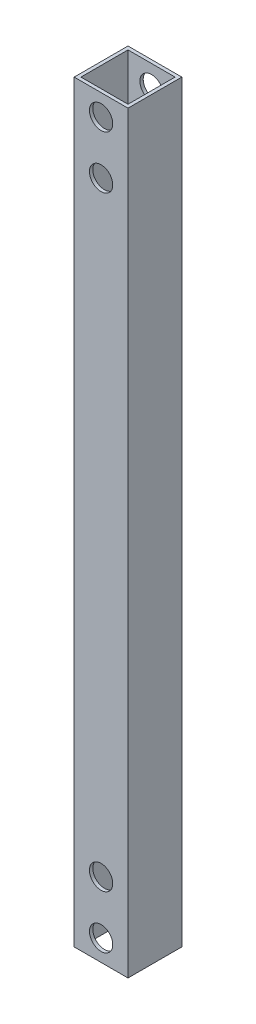
SolidWorks part; units mm, degrees
material "1060 Alloy"
ref_plane "Front Plane" through (0, 0, 0) normal (0, 0, 1) x (1, 0, 0)
ref_plane "Top Plane" through (0, 0, 0) normal (0, 1, 0) x (1, 0, 0)
ref_plane "Right Plane" through (0, 0, 0) normal (1, 0, 0) x (0, 0, -1)
sketch "Sketch1" plane through (0, 0, 0) normal (0, 1, 0) x (1, 0, 0)
  line L1 (-12.7, -12.7) -> (12.7, -12.7)
  line L2 (-12.7, -12.7) -> (-12.7, 12.7)
  line L3 (-12.7, 12.7) -> (12.7, 12.7)
  line L4 (12.7, -12.7) -> (12.7, 12.7)
  line L5 (-12.7, -12.7) -> (12.7, 12.7) construction
  line L6 (-12.7, 12.7) -> (12.7, -12.7) construction
  point P0 (0, 0)
  dimension "D1" = 25.4
extrude "Extrude-Thin1" add sketch "Sketch1" along normal blind 355.6 thin thin type one direction reverse wall 1.5875
sketch "Sketch2" plane through (0, 0, -12.7) normal (0, 0, -1) x (-1, 0, 0)
  line L0 (0, 355.6) -> (0, 0) construction
  line L1 (-12.7, 355.6) -> (12.7, 355.6) construction
  line L2 (-12.7, 0) -> (12.7, 0) construction
  line L3 (12.7, 177.8) -> (-12.7, 177.8) construction
  line L4 (12.7, 355.6) -> (12.7, 0) construction
  line L5 (-12.7, 355.6) -> (-12.7, 0) construction
  point P6 (0, 345.6)
  point P7 (0, 320.6)
  point P14 (0, 35)
  point P15 (0, 10)
  dimension "D1" = 10
  dimension "D2" = 25
hole_wizard "M10 Clearance Hole1" positions "Sketch3" profile "Sketch4" hole size "M10" standard "ANSI Metric" end condition through all
sketch "Sketch3" plane through (0, 0, -12.7) normal (0, 0, -1) x (-1, 0, 0)
  point P0 (0, 345.6)
  point P3 (0, 320.6)
  point P6 (0, 35)
  point P9 (0, 10)
sketch "Sketch4" plane through (0, 345.6, -12.7) normal (1, 0, 0) x (0, 1, 0)
  line L0 (0, 0) -> (0, 25.4)
  line L1 (0, 25.4) -> (5.5, 25.4)
  line L2 (5.5, 25.4) -> (5.5, 0.025)
  line L3 (5.5, 0.025) -> (5.525, 0)
  line L5 (5.525, 0) -> (0, 0)
  line L6 (-5.5, 0.025) -> (-5.525, 0) construction
  line L11 (0, -6.35) -> (0, 107.95) construction
  dimension "Thru Hole Dia." = 11
  dimension "Thru Hole Depth" = 25.4
  dimension "Near C'Sink Dia." = 11.05
  dimension "Near C'Sink Angle" = 90
sketch "Sketch5" plane through (0, 0, 12.7) normal (0, 0, 1) x (1, 0, 0)
  line L0 (0, 0) -> (0, 355.6) construction
  line L1 (-12.7, 0) -> (12.7, 0) construction
  line L2 (-12.7, 355.6) -> (12.7, 355.6) construction
  point P6 (0, 395.1442)
pattern_linear "LPattern1" [suppressed] count 8 spacing 50 of bodies 102
sketch "Sketch6" plane through (0, 0, -12.7) normal (0, 0, -1) x (-1, 0, 0)
  line L0 (12.7, 177.8) -> (-12.7, 177.8) construction
  line L1 (0, 355.6) -> (0, 0) construction
  point P0 (0, 190.3)
  point P1 (0, 165.3)
  dimension "D1" = 12.5
  dimension "D2" = 12.5
